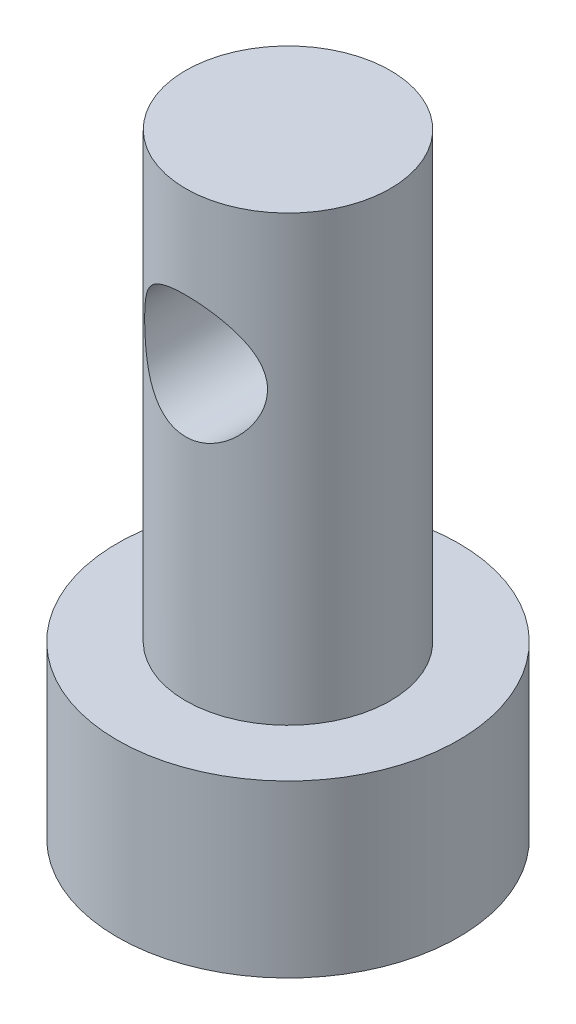
SolidWorks part; units mm, degrees
material "ABS"
ref_plane "Front Plane" through (0, 0, 0) normal (0, 0, 1) x (1, 0, 0)
ref_plane "Top Plane" through (0, 0, 0) normal (0, 1, 0) x (1, 0, 0)
ref_plane "Right Plane" through (0, 0, 0) normal (1, 0, 0) x (0, 0, -1)
sketch "Sketch1" plane through (0, 0, 0) normal (0, 1, 0) x (1, 0, 0)
  circle A0 centre (0, 0) radius 5
  dimension "D1" = 10
extrude "Boss-Extrude1" add sketch "Sketch1" along normal blind 5
sketch "Sketch2" plane through (0, 5, 0) normal (0, 1, 0) x (1, 0, 0)
  circle A0 centre (0, 0) radius 3
  dimension "D1" = 6
extrude "Boss-Extrude2" add sketch "Sketch2" along normal blind 13
sketch "Sketch3" plane through (0, 0, 0) normal (0, -1, 0) x (1, 0, 0)
  circle A0 centre (0, 0) radius 1.9
  dimension "D1" = 3.8
extrude "Cut-Extrude1" cut sketch "Sketch3" against normal blind 10
sketch "Sketch7" plane through (0, 0, 0) normal (0, 0, 1) x (1, 0, 0)
  line L0 (5, 5) -> (-5, 5) construction
  circle A0 centre (0, 13.5) radius 1.8
  point P5 (0, 0)
  dimension "D2" = 3.6
  dimension "D1" = 8.5
extrude "Cut-Extrude5" cut sketch "Sketch7" along normal through all and the other way blind 0.4
